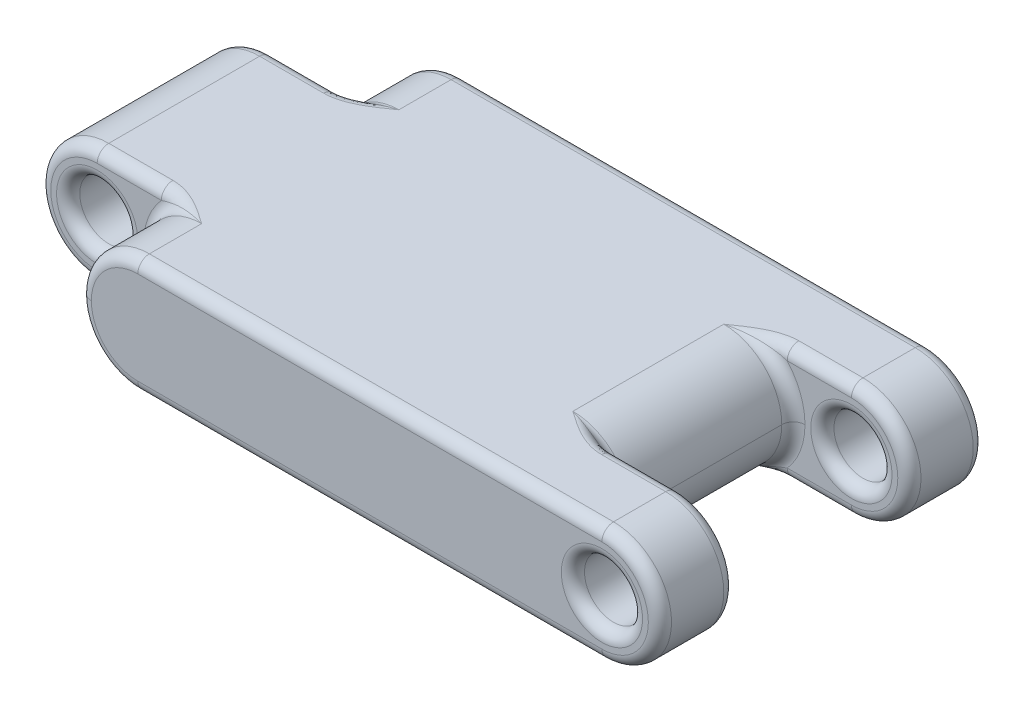
SolidWorks part; units mm, degrees
ref_plane "前视基准面" through (0, 0, 0) normal (0, 0, 1) x (1, 0, 0)
ref_plane "上视基准面" through (0, 0, 0) normal (0, 1, 0) x (1, 0, 0)
ref_plane "右视基准面" through (0, 0, 0) normal (1, 0, 0) x (0, 0, -1)
other "Configuration Table"
sketch "草图1" plane through (0, 0, 0) normal (0, 0, 1) x (1, 0, 0)
  line L0 (0, 0) -> (50, 0) construction
  line L1 (0, 5) -> (50, 5)
  line L2 (0, -5) -> (50, -5)
  arc A0 (0, 5) -> (0, -5) centre (0, 0) ccw
  arc A1 (50, -5) -> (50, 5) centre (50, 0) ccw
extrude "凸台-拉伸1" add sketch "草图1" along normal blind 28
sketch "草图2" plane through (0, 5, 0) normal (0, 1, 0) x (1, 0, 0)
  line L0 (0, -14) -> (60.8354, -14) construction
  line L1 (0, -28) -> (0, 0) construction
  line L2 (60.8354, -14) -> (60.8354, -6.5)
  line L3 (60.8354, -6.5) -> (55, -6.5)
  line L4 (55, -28) -> (55, 0) construction
  line L5 (55, -6.5) -> (45, -6.5)
  line L6 (45, -6.5) -> (45, -21.5)
  line L7 (45, -21.5) -> (55, -21.5)
  line L8 (55, -21.5) -> (55, -6.5)
  line L9 (0, -6.5) -> (-5.7248, -6.5)
  line L10 (-5.7248, -6.5) -> (-5.7248, 1.4813)
  line L11 (-5.7248, 1.4813) -> (0, 1.4813)
  line L12 (0, 1.4813) -> (0, -6.5)
  line L13 (0, -21.5) -> (0, -31.9029)
  line L14 (0, -31.9029) -> (-6.87, -31.9029)
  line L15 (-6.87, -31.9029) -> (-6.5577, -21.5)
  line L16 (-6.5577, -21.5) -> (0, -21.5)
  line L17 (0, -6.5) -> (4.9984, -6.5)
  line L18 (4.9984, -6.5) -> (4.9984, 1.4813)
  line L19 (4.9984, 1.4813) -> (0, 1.4813)
  line L20 (0, -31.9029) -> (4.9984, -31.9029)
  line L21 (4.9984, -31.9029) -> (4.9984, -21.5)
  line L22 (4.9984, -21.5) -> (0, -21.5)
  line M2 (50, 0) -> (0, 0)
  line M3 (0, 0) -> (0, -28)
  line M4 (0, -28) -> (50, -28)
  line M5 (50, -28) -> (50, 0)
extrude "切除-拉伸2" cut sketch "草图2" against normal through all both contours L17 L18 M2 M3 | L12 L11 L10 L9 M3 | L16 L15 L14 L13 M3 | L21 L22 M3 M4 | L6 L0 L5 M5 | L0 L6 L7 M5 | L0 L7 L8 M5 | L0 L8 L5 M5 region at (47.5, 5, 10.25) region at (47.5, 5, 17.75) region at (-2.8624, 5, 2.5094) region at (2.4992, 5, 3.25) region at (2.4992, 5, 24.75) region at (-3.3575, 5, 26.7418) region at (52.5, 5, 10.25) region at (52.5, 5, 17.75)
sketch "草图3" plane through (0, 0, 28) normal (0, 0, 1) x (1, 0, 0)
  circle A0 centre (50, 0) radius 2.5
  circle A1 centre (0, 0) radius 2.5
extrude "切除-拉伸3" cut sketch "草图3" against normal through all both
fillet "圆角1" radius 5 6 edges at (45, -5, 14) (45, 5, 14) (4.9984, -5, 3.25) (4.9984, 5, 3.25) (4.9984, -5, 24.75) (4.9984, 5, 24.75)
fillet "圆角2" radius 1 36 edges at (45, 5, 21.5) (43.5355, 3.5355, 21.5) (43.5355, -3.5355, 21.5) (45, -5, 21.5) (55, 0, 21.5) (52.5, 0, 21.5) (55, 0, 6.5) (45, -5, 6.5) (43.5355, -3.5355, 6.5) (43.5355, 3.5355, 6.5) (45, 5, 6.5) (47.5, 0, 6.5) (55, 0, 0) (29.9992, 5, 0) (6.4628, 3.5355, 0) (6.4628, -3.5355, 0) (29.9992, -5, 0) (52.5, 0, 0) (29.9992, 5, 28) (55, 0, 28) (29.9992, -5, 28) (6.4628, -3.5355, 28) (6.4628, 3.5355, 28) (52.5, 0, 28) (-5, 0, 6.5) (4.9992, -5, 6.5) (6.4628, -3.5355, 6.5) (6.4628, 3.5355, 6.5) (4.9992, 5, 6.5) (2.5, 0, 6.5) (4.9992, 5, 21.5) (6.4628, 3.5355, 21.5) (6.4628, -3.5355, 21.5) (4.9992, -5, 21.5) (-5, 0, 21.5) (2.5, 0, 21.5)
